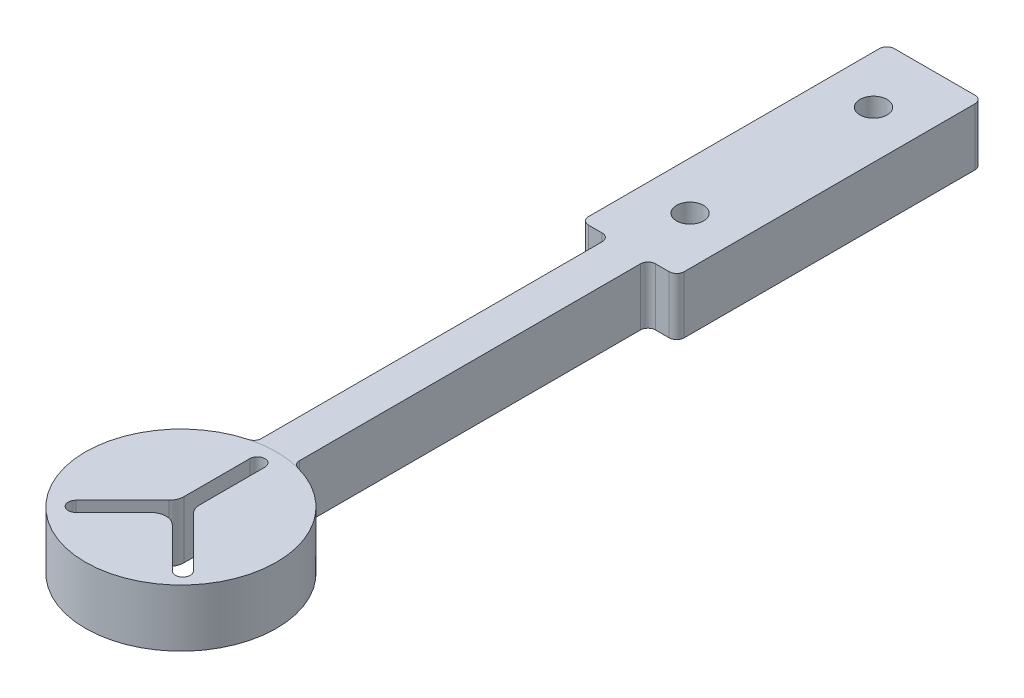
SolidWorks part; units mm, degrees
material "6061-T6 (SS)"
ref_plane "Front Plane" through (0, 0, 0) normal (0, 0, 1) x (1, 0, 0)
ref_plane "Top Plane" through (0, 0, 0) normal (0, 1, 0) x (1, 0, 0)
ref_plane "Right Plane" through (0, 0, 0) normal (1, 0, 0) x (0, 0, -1)
sketch "Sketch1" plane through (0, 0, 0) normal (0, 1, 0) x (1, 0, 0)
  line L0 (-55, 0) -> (55, 0) construction
  line L1 (-7.9375, 50.8) -> (7.9375, 50.8)
  line L2 (-7.9375, 50.8) -> (-7.9375, 0)
  line L3 (-7.9375, 0) -> (-3.175, 0)
  line L4 (7.9375, 50.8) -> (7.9375, 0)
  line L5 (0, -55) -> (0, 55) construction
  line L6 (3.175, 0) -> (7.9375, 0)
  line L8 (-3.175, 0) -> (-3.175, -58.8677)
  line L10 (3.175, 0) -> (3.175, -58.8677)
  arc A0 (-3.175, -58.8677) -> (3.175, -58.8677) centre (0, -74.422) ccw
  dimension "D7" = 31.75
  dimension "D1" = 15.875
  dimension "D2" = 7.9375
  dimension "D3" = 50.8
  dimension "D4" = 74.422
  dimension "D5" = 6.35
  dimension "D6" = 3.175
extrude "Boss-Extrude1" add sketch "Sketch1" along normal blind 9.525
sketch "Sketch2" plane through (0, 9.525, 0) normal (0, 1, 0) x (1, 0, 0)
  line L0 (0, -55) -> (0, 55) construction
  line L1 (7.9375, 50.8) -> (-7.9375, 50.8) construction
  line L2 (-55, 0) -> (55, 0) construction
  circle A0 centre (0, 40.64) radius 2.2479
  circle A1 centre (0, 10.16) radius 2.2479
  dimension "D1" = 4.4958
  dimension "D2" = 4.4958
  dimension "D3" = 10.16
  dimension "D4" = 10.16
extrude "Cut-Extrude1" cut sketch "Sketch2" against normal through all
ref_axis "Axis1" through (0, 11.7998, 74.422) along (0, -1, 0)
sketch "Sketch3" plane through (0, 9.525, 0) normal (0, 1, 0) x (1, 0, 0)
  line L1 (0.06, -75.9191) -> (8.4722, -84.3313)
  line L3 (-1.2446, -73.7034) -> (-1.2446, -61.722)
  line L4 (1.2446, -73.5835) -> (10.2323, -82.5712)
  line L5 (1.2446, -73.5835) -> (1.2446, -61.722)
  line L6 (0, -5.2388) -> (0, 5.2388) construction
  line L8 (-1.2446, -73.7034) -> (-9.7168, -82.1756)
  line L9 (0.06, -75.9191) -> (-7.9566, -83.9357)
  arc A0 (-1.2446, -61.722) -> (1.2446, -61.722) centre (0, -61.722) cw
  arc A1 (10.2323, -82.5712) -> (8.4722, -84.3313) centre (9.3522, -83.4512) cw
  arc A2 (-7.9566, -83.9357) -> (-9.7168, -82.1756) centre (-8.8367, -83.0556) cw
  point P6 (0.6223, -74.422)
  dimension "D3" = 2.4892
  dimension "D5" = 135
  dimension "D6" = 135
  dimension "D1" = 2.4892
  dimension "D2" = 1.2446
  dimension "D4" = 2.4892
extrude "Cut-Extrude2" cut sketch "Sketch3" against normal through all
fillet "Fillet1" radius 1.25 8 edges at (7.9375, 4.7625, -50.8) (-7.9375, 4.7625, -50.8) (-7.9375, 4.7625, 0) (-3.175, 4.7625, 0) (7.9375, 4.7625, 0) (3.175, 4.7625, 0) (3.175, 4.7625, 58.8677) (-3.175, 4.7625, 58.8677)
sketch "Sketch4" plane through (0, 0, 0) normal (0, -1, 0) x (1, 0, 0)
  line L0 (-7.9375, -49.55) -> (-7.9375, -1.25) construction
  line L1 (7.9375, -50.8) -> (-7.9375, -50.8)
  line L2 (7.9375, -50.8) -> (7.9375, 0)
  line L3 (7.9375, 0) -> (-7.9375, 0)
  line L4 (-7.9375, -50.8) -> (-7.9375, 0)
  line L5 (5.2388, 0) -> (-5.2388, 0) construction
  line L6 (7.9375, -1.25) -> (7.9375, -49.55) construction
  line L7 (6.6875, -50.8) -> (-6.6875, -50.8) construction
split line "Split Line1"
sketch "Sketch5" plane through (0, 9.525, 0) normal (0, 1, 0) x (1, 0, 0)
  circle A0 centre (0, -74.422) radius 15.875
split line "Split Line2"
ref_plane "Plane1" through (0, 0, -25.4) normal (0, 0, -1) x (-1, 0, 0)
fillet "Fillet2" radius 2.54 3 edges at (0.06, 4.7625, 75.9191) (1.2446, 4.7625, 73.5835) (-1.2446, 4.7625, 73.7034)
